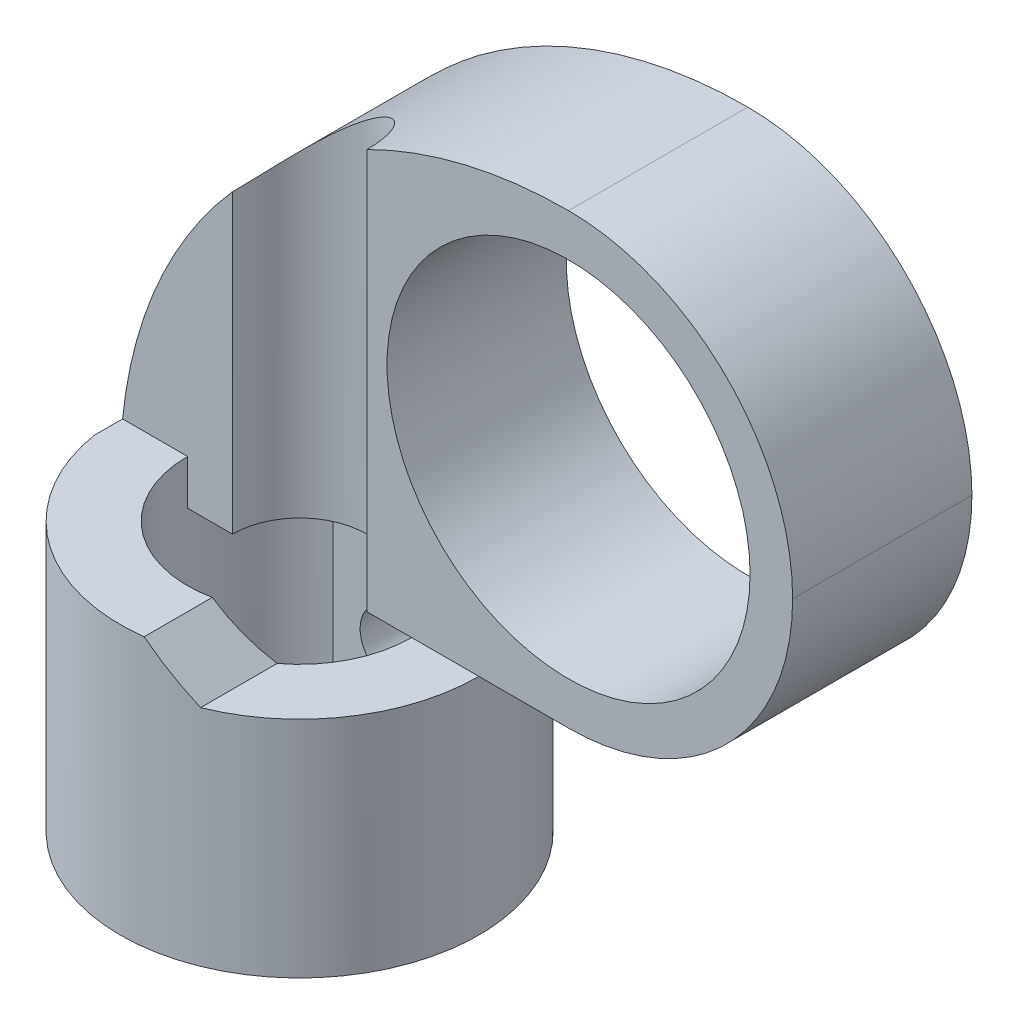
SolidWorks part; units mm, degrees
ref_plane "Front" through (0, 0, 0) normal (0, 0, 1) x (1, 0, 0)
ref_plane "Top" through (0, 0, 0) normal (0, 1, 0) x (1, 0, 0)
ref_plane "Right" through (0, 0, 0) normal (1, 0, 0) x (0, 0, -1)
sketch "草图1" plane through (0, 0, 0) normal (0, 1, 0) x (1, 0, 0)
  circle A0 centre (0, 0) radius 4
  dimension "D1" = 8
extrude "凸台-拉伸1" add sketch "草图1" along normal blind 6
sketch "草图2" plane through (0, 0, 0) normal (0, 1, 0) x (1, 0, 0)
  line L0 (-1.3565, 2.1) -> (1.3565, 2.1)
  arc A0 (-1.3565, 2.1) -> (1.3565, 2.1) centre (0, 0) ccw
  dimension "D1" = 5
  dimension "D2" = 2.1
extrude "切除-拉伸1" cut sketch "草图2" along normal through all
ref_point "点1"
ref_plane "圆心面" through (0, 0, 0) normal (0, 0, 1) x (1, 0, 0)
ref_plane "基准面2" through (0, 0, -4) normal (0, 0, 1) x (1, 0, 0)
sketch "草图4" plane through (0, 0, -4) normal (0, 0, 1) x (1, 0, 0)
  line L0 (0, 11.5) -> (0, -3.1241) construction
  line L1 (-15.8712, 10) -> (17.2764, 10) construction
  line L2 (11, 5) -> (-4, 5)
  line L3 (11, 5) -> (11, 15)
  line L4 (11, 15) -> (-4, 15)
  line L5 (-4, 5) -> (-4, 15)
  line L6 (11, 5) -> (-4, 15) construction
  line L7 (11, 15) -> (-4, 5) construction
  line L8 (2.5, 6) -> (-2.5, 6) construction
  line L9 (-4, 6) -> (-4, 0) construction
  point P3 (3.5, 10)
  dimension "D1" = 10
  dimension "D2" = 4
  dimension "D3" = 15
extrude "凸台-拉伸2" add sketch "草图4" along normal blind 4
sketch "草图5" plane through (0, 0, 0) normal (0, 0, 1) x (1, 0, 0)
  line L0 (11, 10) -> (-14.5535, 10) construction
  line L1 (11, 5) -> (11, 15) construction
  line L2 (0, 19.3577) -> (0, -4.5517) construction
  circle A1 centre (6, 10) radius 4.05
  dimension "D1" = 8.1
  dimension "D2" = 6
extrude "切除-拉伸3" cut sketch "草图5" against normal through all
fillet "圆角1" radius 10 1 edges at (-4, 15, -2)
fillet "圆角2" radius 5 2 edges at (11, 5, -2) (11, 15, -2)
sketch "草图6" plane through (0, 5, 0) normal (0, -1, 0) x (1, 0, 0)
  line L2 (-4, -4) -> (-4, 0)
  line L3 (-4, -4) -> (0, -4)
  arc A1 (-4, 0) -> (0, -4) centre (0, 0) ccw
  circle A2 centre (0, 0) radius 4 construction
extrude "切除-拉伸4" cut sketch "草图6" against normal through all
sketch "草图7" plane through (0, 0, 0) normal (0, -1, 0) x (1, 0, 0)
  circle A0 centre (0, 0) radius 1.5
  dimension "D1" = 3
extrude "切除-拉伸5" cut sketch "草图7" against normal through all
sketch "草图8" plane through (0, 0, -4) normal (0, 0, 1) x (1, 0, 0)
  line L0 (0, 16.1191) -> (0, -2.2327) construction
  line L1 (-4, 0) -> (4, 0) construction
  circle A0 centre (0, 2.5) radius 0.75
  dimension "D1" = 1.5
  dimension "D2" = 2.5
extrude "切除-拉伸7" cut sketch "草图8" along normal blind 3
sketch "草图9" plane through (0, 0, 0) normal (0, 0, 1) x (1, 0, 0)
  line L0 (1.5, 5) -> (1.5, 13.9303) construction
  line L1 (4, 6) -> (1.5, 6)
  line L2 (4, 6) -> (4, 5)
  line L3 (4, 5) -> (1.5, 5)
  line L4 (1.5, 6) -> (1.5, 5)
  line L5 (4, 5) -> (6, 5) construction
extrude "切除-拉伸8" cut sketch "草图9" along normal through all
chamfer "倒角1" distance 1 angle 45 1 edges at (1.5, 6, 2.854)
